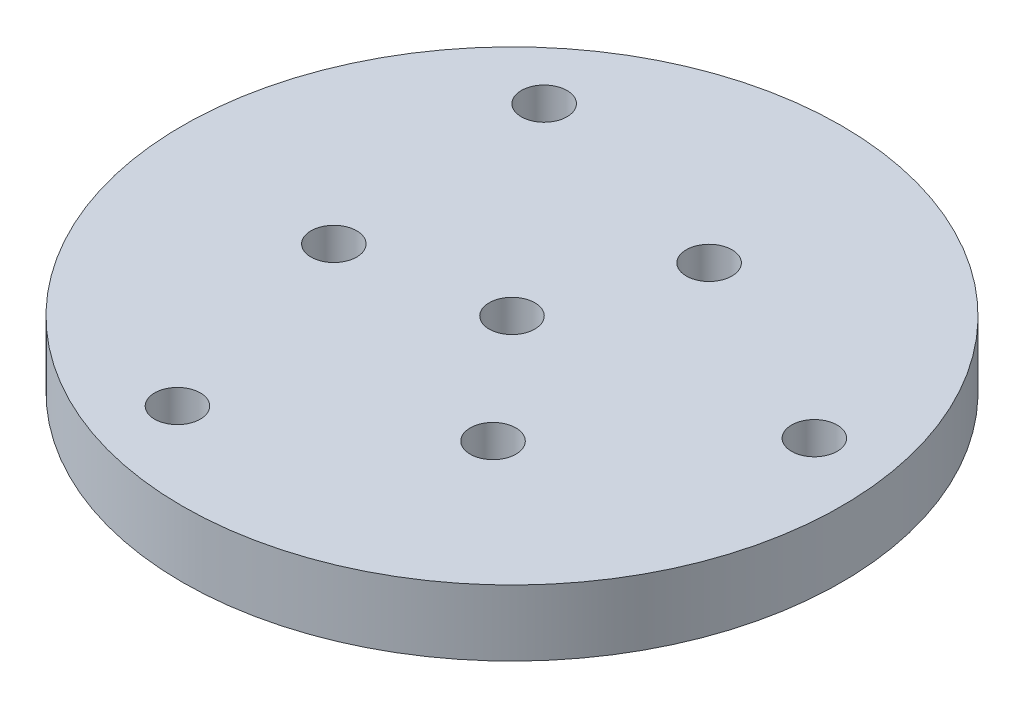
SolidWorks part; units mm, degrees
material "6061-T6 (SS)"
ref_plane "Front Plane" through (0, 0, 0) normal (0, 0, 1) x (1, 0, 0)
ref_plane "Top Plane" through (0, 0, 0) normal (0, 1, 0) x (1, 0, 0)
ref_plane "Right Plane" through (0, 0, 0) normal (1, 0, 0) x (0, 0, -1)
sketch "Sketch1" plane through (0, 0, 0) normal (0, 1, 0) x (1, 0, 0)
  circle A0 centre (0, 0) radius 47.625
  circle A1 centre (0, 0) radius 3.3
  circle A2 centre (0, 25.4) radius 1.5875 construction
  dimension "D1" = 95.25
  dimension "D2" = 6.6
  dimension "D3" = 3.175
  dimension "D4" = 25.4
extrude "Boss-Extrude1" add sketch "Sketch1" along normal mid plane 9.525
ref_plane "Plane1" through (0, 0, 50.8) normal (0, 0, 1) x (1, 0, 0)
sketch "Sketch2" plane through (0, 0, 50.8) normal (0, 0, 1) x (1, 0, 0)
  circle A0 centre (0, 0) radius 1.3526
  dimension "D1" = 2.7051
extrude "Cut-Extrude1" [suppressed] cut sketch "Sketch2" against normal blind 12.7
sketch "Sketch3" plane through (0, 0, 0) normal (0, 0, 1) x (1, 0, 0)
  line L0 (0, 4.7625) -> (0, -4.7625)
  line L1 (47.625, 4.7625) -> (-47.625, 4.7625) construction
  line L2 (-47.625, -4.7625) -> (47.625, -4.7625) construction
pattern_circular "CirPattern1" [suppressed] count 4 over 360 about axis through (0, 4.7625, 0) along (0, -1, 0) of bodies 102
sketch "Sketch4" plane through (0, 4.7625, 0) normal (0, 1, 0) x (1, 0, 0)
  line L0 (0, 0) -> (0, -35.975) construction
  line L1 (-12.9007, -35.4443) -> (0, 0) construction
  line L2 (0, 0) -> (14.286, -17.0253) construction
  circle A0 centre (-12.9007, -35.4443) radius 3.3
  circle A1 centre (-24.2453, 28.8944) radius 3.3
  circle A2 centre (37.146, 6.5498) radius 3.3
  circle A3 centre (14.286, -17.0253) radius 3.3
  circle A4 centre (-21.8874, -3.8593) radius 3.3
  circle A5 centre (7.6014, 20.8847) radius 3.3
  point P12 (0, 0)
  point P19 (0, 0)
  dimension "D1" = 6.6
  dimension "D7" = 6.6
  dimension "D2" = 37.719
  dimension "D3" = 20
  dimension "D5" = 60
  dimension "D6" = 22.225
  dimension "D4" = 3
  dimension "D8" = 3
extrude "Cut-Extrude2" cut sketch "Sketch4" against normal through all
equation "\"Body_Tube_OD\"= 4.024in"
equation "\"Body_Tube_ID\"= 3.90in"
equation "\"SS_Fwd_Bulkhead_OD\"=3.75"
equation "\"D1@Sketch1\"=\"SS_Fwd_Bulkhead_OD\""
equation "\"Bodytube_OD\" = 6.17in"
equation "\"Bodytube_ID\" = 5.998in"
equation "\"Motor_OD\" = 4in"
equation "\"Fwd_Tube_Length\" = 40in"
equation "\"Mid_Tube_Length\" = 1in"
equation "\"Mid_Coupler_Length\" = 13in"
equation "\"Aft_Section_Length\"= 39in"
equation "\"AB_Coupler_OD_Length\"= 1in"
equation "\"AB_Coupling_Section_Length\"= 0.375in"
equation "\"AB_Coupler_Length\"= \"AB_Coupler_OD_Length\" + \"AB_Coupling_Section_Length\" * 2"
equation "\"Cutout_Angle\" = 80"
equation "\"AB_Paddle_Height\" = 0.375in"
equation "\"AB_Coupler_Num_Screws\"= 6"
equation "\"AB_BKHD_Thickness\" = 0.375in"
equation "\"AB_Mount_From_Bottom\" = 23.175in"
equation "\"Num_Cutouts\" = 3"
equation "\"AB_Coupler_OD\"= 6.17in"
equation "\"AB_Coupler_ID\"= 5.75in"
equation "\"AB_Coupler_Surface_Diameter\"= 5.998in"
equation "\"AB_Coupling_Screw_Diameter\"= 0.1065in"
equation "\"AB_Central_Bushing_Length\" = .75in"
equation "\"Lead_Screw_Dist\" = 3.4in"
equation "\"Lead_Screw_Diam\" = 0.386in"
equation "\"Lead_Screw_Length\" = (\"Mid_Coupler_Length\" + 2*0.375in + 2*0.5in)"
equation "\"Paddle_Pin_Offset\" = .25in"
equation "\"Paddle_Pin_Radius\" = 2.25in"
equation "\"SS_Paddle_Pin_Radius\" = 2.25*0.66in"
equation "\"Paddle_Gear_OD\" = 3.2in"
equation "\"Drive_Gear_OD\" = 1.7in"
equation "\"Fwd_BKHD_From_Top\" = 18in"
equation "\"Fin_Thickness\"= .118in"
equation "\"Guiderail_Cutout_Diameter\"= 1.5in"
equation "\"DB9_Hole_Dist\" = 25mm"
equation "\"DB9_Relief_Width\" = 0.47in"
equation "\"DB9_Relief_Hole_Offset\" = 0.09in"
equation "\"Airbrakes_Wire_Hole_Dia\" = .25in"
equation "\"Airbrakes_Wire_Hole_Dist\" = 1.1in"
equation "\"Servo_Gear_Offset\" = 0.5in"
